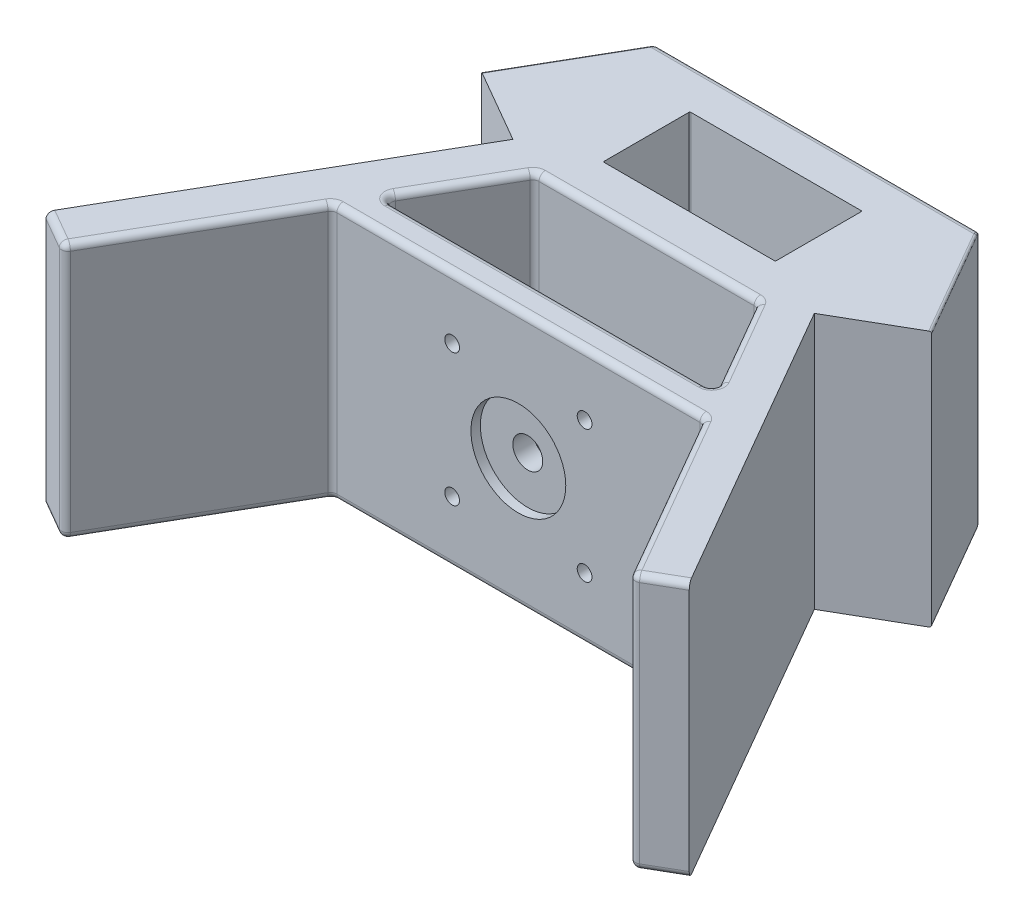
SolidWorks part; units mm, degrees
material "ABS"
ref_plane "Front Plane" through (0, 0, 0) normal (0, 0, 1) x (1, 0, 0)
ref_plane "Top Plane" through (0, 0, 0) normal (0, 1, 0) x (1, 0, 0)
ref_plane "Right Plane" through (0, 0, 0) normal (1, 0, 0) x (0, 0, -1)
sketch "Sketch3" plane through (0, 0, 0) normal (0, 1, 0) x (1, 0, 0)
  line L0 (-52.6837, -6.1) -> (-35.2766, -16.15)
  line L1 (-20.15, 10.15) -> (20.15, 10.15)
  line L2 (-20.15, 10.15) -> (-20.15, -10.15)
  line L3 (-20.15, -10.15) -> (20.15, -10.15)
  line L4 (20.15, 10.15) -> (20.15, -10.15)
  line L5 (-20.15, 10.15) -> (20.15, -10.15) construction
  line L6 (-20.15, -10.15) -> (20.15, 10.15) construction
  line L7 (-35.2766, -16.15) -> (-75.2766, -85.432)
  line L8 (52.6837, -6.1) -> (35.2766, -16.15)
  line L9 (35.2766, -16.15) -> (75.2766, -85.432)
  line L10 (-35.2766, -16.15) -> (35.2766, -16.15) construction
  line L11 (-75.2766, -85.432) -> (75.2766, -85.432) construction
  line L12 (-52.6837, -6.1) -> (52.6837, -6.1) construction
  line L13 (0, 0) -> (0, 50000) construction
  line L14 (-37.5282, 20.15) -> (37.5282, 20.15)
  line L15 (37.5282, 20.15) -> (52.6837, -6.1)
  line L16 (-37.5282, 20.15) -> (-52.6837, -6.1)
  line L17 (-43.9801, -11.125) -> (-25.9235, 20.15) construction
  line L18 (-75.2766, -85.432) -> (-66.6163, -90.432)
  line L19 (-66.6163, -90.432) -> (-43.3595, -50.15)
  line L20 (-43.3595, -50.15) -> (43.3595, -50.15)
  line L21 (43.3595, -50.15) -> (66.6163, -90.432)
  line L22 (66.6163, -90.432) -> (75.2766, -85.432)
  line L23 (-26.039, -20.15) -> (26.039, -20.15)
  line L24 (-21.59, -50.15) -> (21.59, -50.15) construction
  line L25 (-21.59, -50.15) -> (-21.59, -98.15) construction
  line L26 (-21.59, -98.15) -> (21.59, -98.15) construction
  line L27 (21.59, -50.15) -> (21.59, -98.15) construction
  line L28 (-11, -28.15) -> (11, -28.15) construction
  line L29 (-11, -28.15) -> (-11, -45.65) construction
  line L30 (-11, -45.65) -> (11, -45.65) construction
  line L31 (11, -28.15) -> (11, -45.65) construction
  line L32 (26.039, -20.15) -> (39.318, -43.15)
  line L33 (39.318, -43.15) -> (-39.318, -43.15)
  line L34 (-39.318, -43.15) -> (-26.039, -20.15)
  point P0 (0, 0)
  point P15 (0, -85.432)
  point P16 (0, -16.15)
  point P17 (0, -6.1)
  point P21 (0, 20.15)
  point P27 (0, -50.15)
  point P28 (0, -50.15)
  point P37 (0, -28.15)
  dimension "D1" = 40.3
  dimension "D2" = 20.3
  dimension "D3" = 300
  dimension "D4" = 20.1
  dimension "D5" = 80
  dimension "D6" = 10
  dimension "D7" = 10
  dimension "D8" = 6
  dimension "D9" = 10
  dimension "D10" = 43.18
  dimension "D11" = 48
  dimension "D12" = 22
  dimension "D13" = 17.5
  dimension "D14" = 22
  dimension "D15" = 30
  dimension "D16" = 10
  dimension "D17" = 7
extrude "Boss-Extrude1" add sketch "Sketch3" along normal blind 55
extrude "Boss-Extrude3" add sketch "Sketch3<2>" against normal blind 5 contours L21 L22 L9 L8 L15 L14 L16 L0 L7 L18 L19 L20 L1 L4 L3 L2 L33 L34 L23 L32 | L4 L1 L2 L3 region at (-43.4882, 0, -6.091) region at (0, 0, 0)
sketch "Sketch3<2>" plane through (0, 0, 0) normal (0, 1, 0) x (1, 0, 0) same geometry as "Sketch3"
fillet "Fillet2" radius 0.25 4 edges at (-20.15, 27.5, 10.15) (20.15, 27.5, 10.15) (-20.15, 27.5, -10.15) (20.15, 27.5, -10.15)
fillet "Fillet3" radius 1.5 30 edges at (-54.9879, 55, 70.291) (-32.6785, 55, 31.65) (54.9879, -5, 70.291) (0, -5, 20.15) (0, 55, 50.15) (0, 55, 43.15) (0, 55, 20.15) (0, -5, 50.15) (32.6785, -5, 31.65) (-32.6785, -5, 31.65) (0, 55, -20.15) (70.9465, 55, 87.932) (-70.9465, 55, 87.932) (54.9879, 55, 70.291) (32.6785, 55, 31.65) (70.9465, -5, 87.932) (-54.9879, -5, 70.291) (-70.9465, -5, 87.932) (0, -5, -20.15) (0, -5, 43.15) (-66.6163, 25, 90.432) (66.6163, 25, 90.432) (37.5282, 25, -20.15) (-37.5282, 25, -20.15) (-43.3595, 25, 50.15) (43.3595, 25, 50.15) (-39.318, 25, 43.15) (39.318, 25, 43.15) (26.039, 25, 20.15) (-26.039, 25, 20.15)
sketch "Sketch5" plane through (0, 0, 50.15) normal (0, 0, 1) x (1, 0, 0)
  line L0 (-42.4935, 53.5) -> (42.4935, -3.5) construction
  line L1 (-42.4935, -3.5) -> (42.4935, 53.5) construction
  line L2 (-15.5, 40.5) -> (15.5, 9.5) construction
  line L3 (-15.5, 9.5) -> (15.5, 40.5) construction
  circle A0 centre (0, 25) radius 11.1
  circle A1 centre (-15.5, 40.5) radius 1.725
  circle A2 centre (15.5, 40.5) radius 1.725
  circle A3 centre (15.5, 9.5) radius 1.725
  circle A4 centre (-15.5, 9.5) radius 1.725
  circle A5 centre (0, 25) radius 3.5
  point P11 (0, 25)
  dimension "D1" = 22.2
  dimension "D2" = 3.45
  dimension "D5" = 7
  dimension "D3" = 31
  dimension "D4" = 31
extrude "Cut-Extrude1" cut sketch "Sketch5" against normal blind 2.2 contours A0 A5 region at (-10.786, 25, 50.15)
extrude "Cut-Extrude2" cut sketch "Sketch5<3>" against normal up to surface (7 mm away) contours A1 | A2 | A3 | A4 | A5 region at (-15.5, 40.5, 50.15) region at (15.5, 40.5, 50.15) region at (15.5, 9.5, 50.15) region at (-15.5, 9.5, 50.15) region at (0, 25, 50.15) up to face at (0, 25, 43.15)
sketch "Sketch5<3>" plane through (0, 0, 50.15) normal (0, 0, 1) x (1, 0, 0) same geometry as "Sketch5"
sketch "Sketch6" plane through (0, 0, 43.15) normal (0, 0, -1) x (-1, 0, 0)
  circle A0 centre (15.5, 40.5) radius 3.6
  circle A1 centre (-15.5, 40.5) radius 3.6
  circle A2 centre (-15.5, 9.5) radius 3.6
  circle A3 centre (15.5, 9.5) radius 3.6
  circle A4 centre (15.5, 9.5) radius 1.725 construction
  circle A5 centre (15.5, 40.5) radius 1.725 construction
  circle A6 centre (-15.5, 40.5) radius 1.725 construction
  circle A7 centre (-15.5, 9.5) radius 1.725 construction
  dimension "D1" = 7.2
extrude "Cut-Extrude3" [suppressed] cut sketch "Sketch6" against normal blind 3.5 contours A0 | A1 | A2 | A3
fillet "Fillet4" radius 0.5 12 edges at (-37.4122, 54.25, -19.949) (-38.1701, 54.9489, -19.0382) (-37.4122, -4.25, -19.949) (-38.1701, -4.9489, -19.0382) (37.4122, -4.25, -19.949) (38.1701, -4.9489, -19.0382) (37.4122, 54.25, -19.949) (38.1701, 54.9489, -19.0382) (-45.539, 55, -6.275) (-45.539, -5, -6.275) (45.539, -5, -6.275) (45.539, 55, -6.275)
